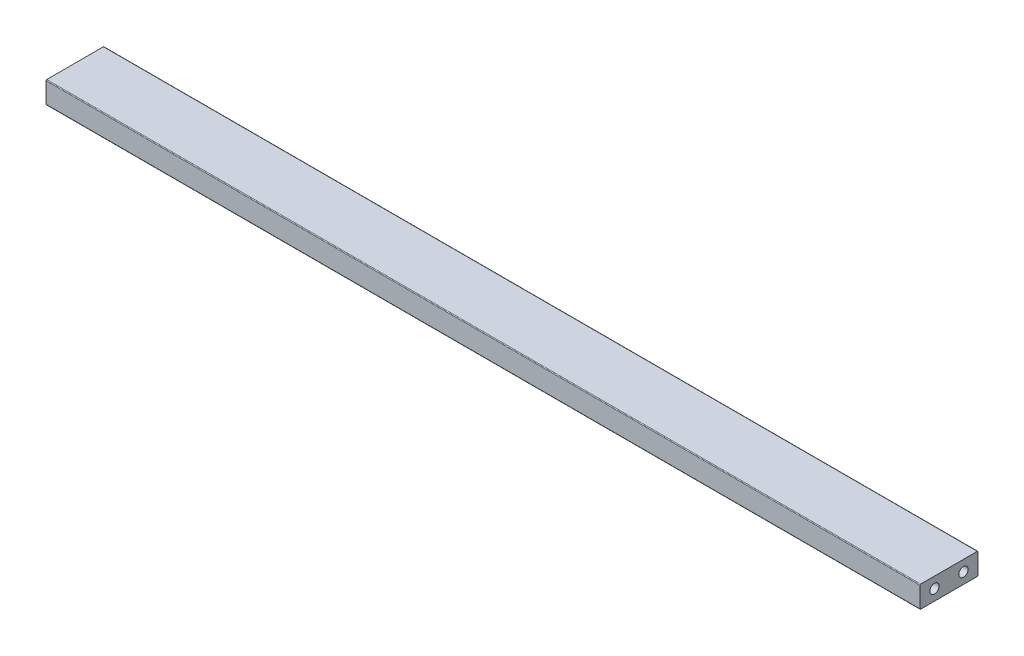
SolidWorks part; units mm, degrees
ref_plane "Front Plane" through (0, 0, 0) normal (0, 0, 1) x (1, 0, 0)
ref_plane "Top Plane" through (0, 0, 0) normal (0, 1, 0) x (1, 0, 0)
ref_plane "Right Plane" through (0, 0, 0) normal (1, 0, 0) x (0, 0, -1)
sketch "Sketch1" plane through (0, 0, 0) normal (0, 1, 0) x (1, 0, 0)
  line L1 (191.135, -12.7) -> (-191.135, -12.7)
  line L2 (191.135, -12.7) -> (191.135, 12.7)
  line L3 (191.135, 12.7) -> (-191.135, 12.7)
  line L4 (-191.135, -12.7) -> (-191.135, 12.7)
  line L5 (191.135, -12.7) -> (-191.135, 12.7) construction
  line L6 (191.135, 12.7) -> (-191.135, -12.7) construction
  point P0 (0, 0)
  dimension "Length" = 382.27
  dimension "Width" = 25.4
sketch "Sketch2" plane through (0, 0, 0) normal (1, 0, 0) x (0, 0, -1)
  line L0 (12.7, 4.7625) -> (12.7, -4.7625) construction
  point P2 (12.7, 0)
  dimension "Thickness" = 9.525
sketch "Sketch3" plane through (0, 0, 0) normal (0, 1, 0) x (1, 0, 0)
  line L1 (-191.135, 12.7) -> (191.135, 12.7)
  line L2 (-191.135, 12.7) -> (-191.135, -12.7)
  line L3 (-191.135, -12.7) -> (191.135, -12.7)
  line L4 (191.135, 12.7) -> (191.135, -12.7)
extrude "Boss-Extrude1" add sketch "Sketch3" against normal up to vertex (4.7625 mm away) and the other way up to vertex (4.7625 mm away) up to point (0, -4.7625, -12.7) other way up to point (0, 4.7625, -12.7)
fillet "Fillet1" radius 0.3143 4 edges at (0, -4.7625, 12.7) (0, -4.7625, -12.7) (0, 4.7625, -12.7) (0, 4.7625, 12.7)
sketch "Sketch4" plane through (-191.135, 0, 0) normal (-1, 0, 0) x (0, 0, 1)
  line L0 (0, 0) -> (6.35, 0) construction
  line L1 (0, 0) -> (-6.35, 0) construction
hole_wizard "Tap Drill for #10-32 Tap1" positions "Sketch5" profile "Sketch6" hole size "#10-32" standard "ANSI Inch"
sketch "Sketch5" plane through (-191.135, 0, 0) normal (-1, 0, 0) x (0, 0, 1)
  point P0 (-6.35, 0)
  point P3 (6.35, 0)
sketch "Sketch6" plane through (-191.135, 0, -6.35) normal (0, 1, 0) x (0, 0, 1)
  line L0 (0, 0) -> (0, 26.6133)
  line L1 (0, 26.6133) -> (2.0193, 25.4)
  line L2 (2.0193, 25.4) -> (2.0193, 0)
  line L5 (2.0193, 0) -> (0, 0)
  line L10 (0, 26.6133) -> (-2.0193, 25.4) construction
  line L11 (0, -6.35) -> (0, 107.95) construction
  dimension "Hole Dia." = 4.0386
  dimension "Hole Depth" = 25.4
  dimension "Drill Angle" = 118
hole_wizard "Tap Drill for #10-32 Tap2" positions "Sketch7" profile "Sketch8" hole size "#10-32" standard "ANSI Inch"
sketch "Sketch7" plane through (191.135, 0, 0) normal (1, 0, 0) x (0, 0, -1)
  point P0 (-6.35, 0)
  point P3 (6.35, 0)
sketch "Sketch8" plane through (191.135, 0, 6.35) normal (0, 1, 0) x (0, 0, -1)
  line L0 (0, 0) -> (0, 26.6133)
  line L1 (0, 26.6133) -> (2.0193, 25.4)
  line L2 (2.0193, 25.4) -> (2.0193, 0)
  line L5 (2.0193, 0) -> (0, 0)
  line L10 (0, 26.6133) -> (-2.0193, 25.4) construction
  line L11 (0, -6.35) -> (0, 107.95) construction
  dimension "Hole Dia." = 4.0386
  dimension "Hole Depth" = 25.4
  dimension "Drill Angle" = 118
equation "\"D1@Fillet1\" = \"Thickness@Sketch2\" * .033"
